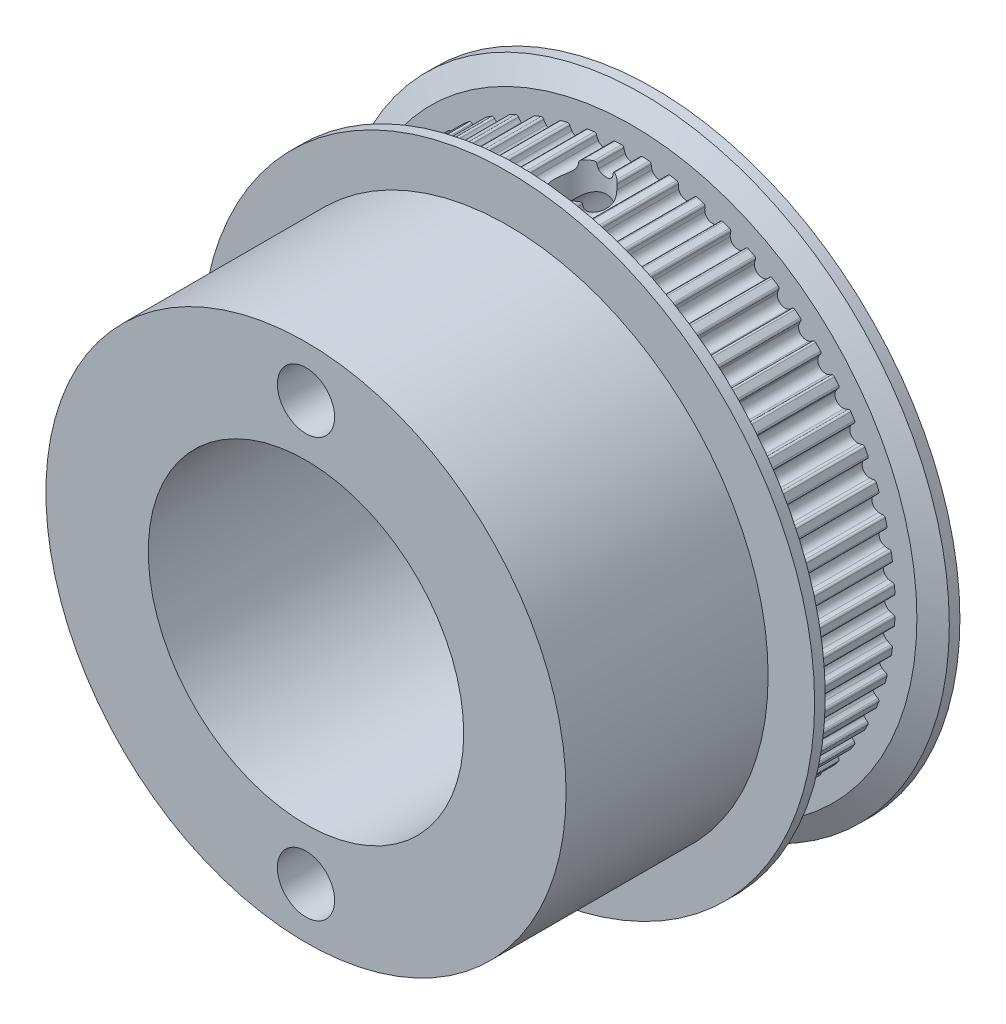
SolidWorks part; units mm, degrees
ref_plane "Front Plane" through (0, 0, 0) normal (0, 0, 1) x (1, 0, 0)
ref_plane "Top Plane" through (0, 0, 0) normal (0, 1, 0) x (1, 0, 0)
ref_plane "Right Plane" through (0, 0, 0) normal (1, 0, 0) x (0, 0, -1)
sketch "Sketch1" plane through (0, 0, 0) normal (0, 0, 1) x (1, 0, 0)
  line L1 (-1.9027, 18.097) -> (1.9027, 18.097) construction
  line L4 (0, 0) -> (0, 18.097) construction
  line L5 (0, 18.097) -> (0, 19.7034) construction
  line L6 (0, 19.101) -> (1.9973, 18.9963) construction
  line L7 (1.9973, 18.9963) -> (2.8966, 18.9017) construction
  line L8 (1.9973, 18.9963) -> (1.9027, 18.097) construction
  line L9 (-1.9973, 18.9963) -> (-1.9027, 18.097) construction
  line L10 (-1.9707, 18.7437) -> (-2.31, 21.971)
  line L11 (-2.31, 21.971) -> (2.31, 21.971)
  line L12 (2.31, 21.971) -> (1.9707, 18.7437)
  circle A0 centre (0, 0) radius 19.101 construction
  circle A1 centre (0, 0) radius 21.971 construction
  circle A2 centre (0, 0) radius 18.847 construction
  arc A3 (-0.4989, 18.4088) -> (0.4989, 18.4088) centre (0, 18.652) ccw
  arc A4 (-0.4989, 18.4088) -> (-0.5897, 18.7039) centre (0.4, 18.847) cw
  arc A5 (-1.9707, 18.7437) -> (-0.7441, 18.8323) centre (0, 0) cw
  arc A6 (-0.5897, 18.7039) -> (-0.7441, 18.8323) centre (-0.7382, 18.6824) ccw
  arc A7 (1.9707, 18.7437) -> (0.7441, 18.8323) centre (0, 0) ccw
  arc A8 (0.5897, 18.7039) -> (0.7441, 18.8323) centre (0.7382, 18.6824) cw
  arc A9 (0.4989, 18.4088) -> (0.5897, 18.7039) centre (-0.4, 18.847) ccw
  point P6 (0, 20.9083)
  point P11 (0, 19.101)
  point P13 (0, 21.971)
  point P14 (0, 18.847)
  dimension "D1" = 1.2049
  dimension "D2" = 0.6024
sketch "Sketch2" plane through (0, 0, 0) normal (1, 0, 0) x (0, 0, -1)
  line L0 (-9.1313, 3.175) -> (9.1313, 3.175)
  line L1 (-9.1313, 3.175) -> (-9.1313, 15.52)
  line L2 (-9.1313, 15.52) -> (-1.2787, 15.52)
  line L3 (-1.2787, 15.52) -> (-1.2787, 21.971)
  line L4 (-1.2787, 21.971) -> (0.2413, 21.971) construction
  line L5 (0.2413, 21.971) -> (0.2413, 18.847) construction
  line L6 (0.2413, 18.847) -> (7.6113, 18.847)
  line L7 (7.6113, 18.847) -> (7.6113, 21.971) construction
  line L8 (7.6113, 21.971) -> (9.1313, 21.971) construction
  line L9 (9.1313, 21.971) -> (9.1313, 3.175)
  line L10 (-9.1313, 0) -> (9.1313, 0) construction
  line L11 (8.3713, 21.971) -> (7.6113, 20.409)
  line L12 (0.2413, 20.409) -> (-0.5187, 21.971)
  line L13 (-1.2787, 21.971) -> (-0.5187, 21.971)
  line L14 (0.2413, 20.409) -> (0.2413, 18.847)
  line L15 (7.6113, 18.847) -> (7.6113, 20.409)
  line L16 (8.3713, 21.971) -> (9.1313, 21.971)
  arc A0 (0.2413, 20.409) -> (-0.5187, 21.971) centre (-1.7439, 20.409) ccw construction
  arc A1 (7.6113, 20.409) -> (8.3713, 21.971) centre (9.5965, 20.409) cw construction
  point P12 (0.2413, 20.409)
  point P14 (-0.5187, 21.971)
  point P20 (7.6113, 20.409)
  point P21 (8.3713, 21.971)
  point P25 (7.6113, 0)
  point P26 (0.2413, 0)
revolve "Revolve1" add sketch "Sketch2" angle 360 mid plane about L10
sketch "Sketch3" plane through (0, 0, 0) normal (0, 0, 1) x (1, 0, 0)
  line L6 (2.31, 21.971) -> (-2.31, 21.971)
  line L7 (1.9707, 18.7437) -> (2.31, 21.971)
  line L8 (-2.31, 21.971) -> (-1.9707, 18.7437)
  line L9 (2.31, 21.971) -> (-2.31, 21.971)
  line L10 (1.9707, 18.7437) -> (2.31, 21.971)
  line L11 (-2.31, 21.971) -> (-1.9707, 18.7437)
  arc A8 (1.9707, 18.7437) -> (0.7441, 18.8323) centre (0, 0) ccw
  arc A9 (0.7441, 18.8323) -> (0.5897, 18.7039) centre (0.7382, 18.6824) ccw
  arc A10 (0.4989, 18.4088) -> (0.5897, 18.7039) centre (-0.4, 18.847) ccw
  arc A11 (-0.4989, 18.4088) -> (0.4989, 18.4088) centre (0, 18.652) ccw
  arc A12 (-0.5897, 18.7039) -> (-0.4989, 18.4088) centre (0.4, 18.847) ccw
  arc A13 (-0.5897, 18.7039) -> (-0.7441, 18.8323) centre (-0.7382, 18.6824) ccw
  arc A14 (-0.7441, 18.8323) -> (-1.9707, 18.7437) centre (0, 0) ccw
  arc A15 (1.9707, 18.7437) -> (0.7441, 18.8323) centre (0, 0) ccw
  arc A16 (0.7441, 18.8323) -> (0.5897, 18.7039) centre (0.7382, 18.6824) ccw
  arc A17 (0.4989, 18.4088) -> (0.5897, 18.7039) centre (-0.4, 18.847) ccw
  arc A18 (-0.4989, 18.4088) -> (0.4989, 18.4088) centre (0, 18.652) ccw
  arc A19 (-0.5897, 18.7039) -> (-0.4989, 18.4088) centre (0.4, 18.847) ccw
  arc A20 (-0.5897, 18.7039) -> (-0.7441, 18.8323) centre (-0.7382, 18.6824) ccw
  arc A21 (-0.7441, 18.8323) -> (-1.9707, 18.7437) centre (0, 0) ccw
  dimension "D1" = 0
extrude "Cut-Extrude1" cut sketch "Sketch3" against normal up to vertex (7.6113 mm away) from vertex up to point (0, 18.847, -7.6113) starting at point (0, 18.847, -0.2413)
pattern_circular "CirPattern1" count 60 over 360 about axis through (0, 0, 9.1313) along (0, 0, 1) of "Cut-Extrude1"
sketch "Sketch4" plane through (0, 0, 0) normal (1, 0, 0) x (0, -1, 0)
  line L0 (0, -1.2787) -> (0, -9.1313) construction
  line L1 (-15.52, -1.2787) -> (15.52, -1.2787) construction
  line L2 (-15.52, -9.1313) -> (15.52, -9.1313) construction
  circle A0 centre (0, -5.205) radius 1.7526
extrude "Cut-Extrude2" cut sketch "Sketch4" along normal through all
ref_plane "Plane1" through (0, 0, 5.205) normal (0, 0, 1) x (1, 0, 0)
sketch "Sketch5" plane through (0, 0, 5.205) normal (0, 0, 1) x (1, 0, 0)
  line L0 (0, 0.1664) -> (0, 15.52) construction
  line L1 (3.175, -1.3716) -> (3.175, 0)
  line L2 (3.556, -1.7526) -> (15.0397, -1.7526)
  line L3 (3.175, 0) -> (15.52, 0) construction
  line L4 (3.175, 0) -> (15.4207, 0)
  line L5 (15.4207, 0) -> (15.4207, -1.3716)
  line L6 (3.556, -1.7526) -> (3.175, -1.3716)
  line L7 (15.4207, -1.3716) -> (15.0397, -1.7526)
  circle A0 centre (0, 0) radius 15.52 construction
  circle A1 centre (0, 0) radius 3.175 construction
  point P2 (3.175, -1.7526)
  point P11 (15.4207, -1.7526)
revolve "Revolve2" add sketch "Sketch5" angle 360 mid plane about L4
sketch "Sketch6" plane through (15.4207, 5.3841, 0) normal (-1, 0, 0) x (0, -1, 0)
  line L1 (5.3841, 6.2169) -> (4.5078, 5.7109)
  line L2 (4.5078, 5.7109) -> (4.5078, 4.6991)
  line L3 (4.5078, 4.6991) -> (5.3841, 4.1931)
  line L4 (5.3841, 4.1931) -> (6.2604, 4.6991)
  line L5 (6.2604, 4.6991) -> (6.2604, 5.7109)
  line L6 (6.2604, 5.7109) -> (5.3841, 6.2169)
  circle A0 centre (5.3841, 5.205) radius 0.8763 construction
  dimension "D1" = 1.7526
extrude "Cut-Extrude3" cut sketch "Sketch6" along normal blind 1.3144
pattern_circular "CirPattern2" count 2 over 90 about axis through (0, 0, 9.1313) along (0, 0, 1) of "Cut-Extrude2", "Revolve2", "Cut-Extrude3"
chamfer "Chamfer1" distance 0.776 angle 45 2 edges at (3.175, 0, 9.1313) (15.52, 0, 9.1313)
ref_axis "Center Axis 1" through (0, 0, -9.1313) along (0, 0, 1)
ref_plane "Contact Plane 1" through (0, 0, 9.1313) normal (0, 0, 1) x (1, 0, 0)
ref_plane "Contact Plane 2" through (0, 0, -9.1313) normal (0, 0, -1) x (-1, 0, 0)
sketch "Sketch7" plane through (0, 0, 0) normal (0, 1, 0) x (1, 0, 0)
  line L0 (-21.971, -1.2787) -> (21.971, -1.2787) construction
  line L1 (-21.971, -1.2787) -> (25.9937, -1.2787)
  line L2 (-21.971, -1.2787) -> (-21.971, -11.9749)
  line L3 (-21.971, -11.9749) -> (25.9937, -11.9749)
  line L4 (25.9937, -1.2787) -> (25.9937, -11.9749)
extrude "Cut-Extrude4" cut sketch "Sketch7" against normal through all both and the other way through all
sketch "Sketch8" plane through (0, 0, -9.1313) normal (0, 0, -1) x (-1, 0, 0)
  line L0 (9.5368, 0) -> (-9.934, 0) construction
  circle A0 centre (0, -15) radius 2.05
  circle A2 centre (0, 15) radius 2.05
  dimension "D3" = 4.1
  dimension "D1" = 15
extrude "Cut-Extrude5" cut sketch "Sketch8" against normal up to surface (10.41 mm away) up to face at (21.971, 0, 1.2787)
sketch "Sketch9" plane through (0, 0, 0) normal (0, 1, 0) x (1, 0, 0)
  line L0 (-21.971, 9.1313) -> (-21.971, -1.2787) construction
  line L1 (-21.971, -1.2787) -> (21.971, -1.2787) construction
  circle A0 centre (0, 3.9263) radius 1.8415
  point P8 (-21.971, 3.9263)
  dimension "D1" = 3.683
extrude "Cut-Extrude6" cut sketch "Sketch9" along normal through all
sketch "Sketch10" plane through (0, 0, 1.2787) normal (0, 0, 1) x (1, 0, 0)
  circle A0 centre (0, 0) radius 11.303
  dimension "D1" = 22.606
extrude "Cut-Extrude7" cut sketch "Sketch10" against normal blind 7.239
sketch "Sketch11" plane through (0, 0, 1.2787) normal (0, 0, 1) x (1, 0, 0)
  line L0 (0, 0) -> (0, 17.05) construction
  circle A0 centre (0, 0) radius 18.6375
  circle A1 centre (0, 0) radius 11.303 construction
  circle A2 centre (0, 0) radius 11.303
  circle A3 centre (0, 15) radius 2.05 construction
  circle A4 centre (0, 15) radius 2.05
  circle A5 centre (0, -15) radius 2.05 construction
  circle A6 centre (0, -15) radius 2.05
  circle A8 centre (0, 0) radius 17.05 construction
  dimension "D1" = 1.5875
extrude "Boss-Extrude1" add sketch "Sketch11" along normal blind 14.478
equation "\"D2@Sketch1\" = \"D1@Sketch1\"/2"
equation "\"D1@Sketch6\" = \"Set Screw@Sketch4\" / 2"
equation "\"D1@Cut-Extrude3\" = \"D1@Sketch6\"*.75"
equation "\"D1@Chamfer1\"=\"Hub Dia@Sketch2\"*.025"
